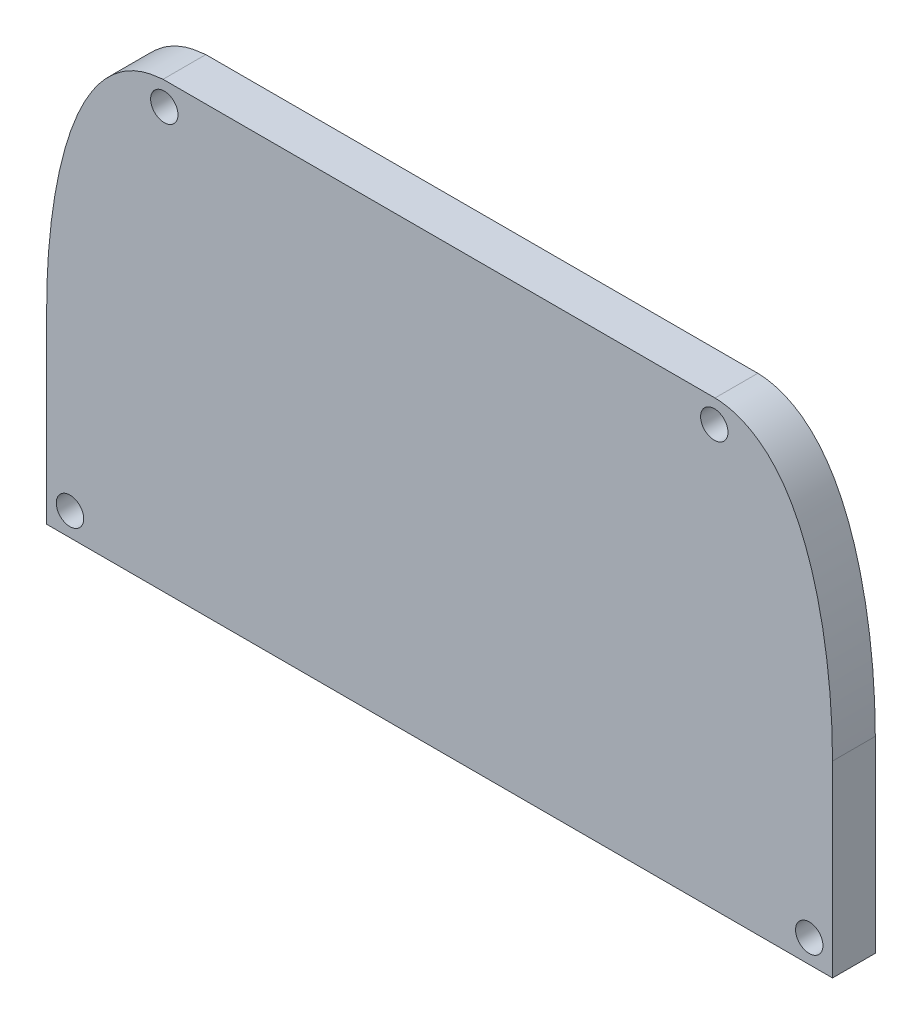
SolidWorks part; units mm, degrees
ref_plane "Front Plane" through (0, 0, 0) normal (0, 0, 1) x (1, 0, 0)
ref_plane "Top Plane" through (0, 0, 0) normal (0, 1, 0) x (1, 0, 0)
ref_plane "Right Plane" through (0, 0, 0) normal (1, 0, 0) x (0, 0, -1)
sketch "Sketch1" plane through (0, 0, 0) normal (0, 0, 1) x (1, 0, 0)
  line L0 (-29, 4.9329) -> (-29, 18.9593) construction
  line L1 (-29, 4.9329) -> (29, 4.9329) construction
  line L2 (29, 18.9593) -> (29, 4.9329) construction
  line L3 (-20.2196, 37.9329) -> (20.1267, 37.9329) construction
  line L4 (-29, 4.9329) -> (-29, 18.9593) construction
  line L5 (-29, 4.9329) -> (29, 4.9329) construction
  line L6 (29, 18.9593) -> (29, 4.9329) construction
  line L7 (-20.2196, 37.9329) -> (20.1267, 37.9329) construction
  line L8 (-20.2031, 37.6329) -> (20.1172, 37.6329)
  line L9 (28.7, 18.9573) -> (28.7, 5.2329)
  line L10 (-28.7, 5.2329) -> (28.7, 5.2329)
  line L11 (-28.7, 5.2329) -> (-28.7, 18.9574)
  spline S0 degree 2 poles (-31.9692, -1981.0344) (-29.7545, -9.9281) (-28.9753, 20.3809) (-28.956, 21.1325) (-28.9167, 21.8007) (-28.8758, 22.4979) (-28.8098, 23.2181) (-28.7437, 23.9403) (-28.6586, 24.6315) (-28.4799, 26.084) (-28.2121, 27.4233) (-27.9175, 28.8968) (-27.5367, 30.1575) (-27.0955, 31.6182) (-26.54, 32.811) (-26.2171, 33.5043) (-25.8726, 34.0804) (-25.4881, 34.7234) (-25.0615, 35.2597) (-24.6042, 35.8346) (-24.0818, 36.3005) (-23.8077, 36.5449) (-23.5308, 36.7481) (-23.2417, 36.9603) (-22.9324, 37.1389) (-22.6103, 37.3249) (-22.2891, 37.4608) (-21.9641, 37.5983) (-21.6205, 37.6954) (-21.3002, 37.7859) (-20.9286, 37.8453) (-20.7579, 37.8725) (-20.5753, 37.8935) (-17.3507, 38.2646) (1967.8393, 255.5742) knots -3.936313 -3.936313 -3.936313 0.0625 0.0625 0.125 0.125 0.1875 0.1875 0.25 0.25 0.375 0.375 0.5 0.5 0.625 0.625 0.6875 0.6875 0.75 0.75 0.8125 0.8125 0.84375 0.84375 0.875 0.875 0.90625 0.90625 0.9375 0.9375 0.96875 0.96875 0.984375 0.984375 2.300936 2.300936 2.300936 only from (-29, 18.9593) to (-20.2196, 37.9329) construction
  spline S1 degree 2 poles (-1977.1742, 141.4907) (9.4885, 38.8169) (20.4852, 37.9083) (20.6703, 37.893) (20.8404, 37.8684) (21.2069, 37.8154) (21.537, 37.7239) (21.7643, 37.6608) (21.9906, 37.5773) (22.4388, 37.4119) (22.8602, 37.1763) (23.1749, 37.0004) (23.4635, 36.7958) (23.748, 36.5941) (24.0261, 36.3514) (24.5413, 35.902) (25.0135, 35.3191) (25.3594, 34.8921) (25.6787, 34.3934) (25.9078, 34.0356) (26.1167, 33.6528) (26.3118, 33.295) (26.5032, 32.8894) (27.0665, 31.6959) (27.5124, 30.2375) (27.9021, 28.9627) (28.2027, 27.4702) (28.4749, 26.1185) (28.6558, 24.6546) (28.7415, 23.9614) (28.8083, 23.2347) (28.8748, 22.5113) (28.9161, 21.8119) (28.9558, 21.1393) (28.9752, 20.3865) (29.7594, -10.0157) (31.6782, -1981.0151) knots -1.71869 -1.71869 -1.71869 0.015625 0.015625 0.03125 0.03125 0.0625 0.0625 0.083333 0.083333 0.125 0.125 0.15625 0.15625 0.1875 0.1875 0.25 0.25 0.3 0.3 0.3375 0.3375 0.375 0.375 0.5 0.5 0.625 0.625 0.75 0.75 0.8125 0.8125 0.875 0.875 0.9375 0.9375 4.930379 4.930379 4.930379 only from (20.1267, 37.9329) to (29, 18.9593) construction
  spline S2 degree 2 poles (-29, 18.9593) (-28.9875, 19.9072) (-28.9753, 20.3809) (-28.956, 21.1325) (-28.9167, 21.8007) (-28.8758, 22.4979) (-28.8098, 23.2181) (-28.7437, 23.9403) (-28.6586, 24.6315) (-28.4799, 26.084) (-28.2121, 27.4233) (-27.9175, 28.8968) (-27.5367, 30.1575) (-27.0955, 31.6182) (-26.54, 32.811) (-26.2171, 33.5043) (-25.8726, 34.0804) (-25.4881, 34.7234) (-25.0615, 35.2597) (-24.6042, 35.8346) (-24.0818, 36.3005) (-23.8077, 36.5449) (-23.5308, 36.7481) (-23.2417, 36.9603) (-22.9324, 37.1389) (-22.6103, 37.3249) (-22.2891, 37.4608) (-21.9641, 37.5983) (-21.6205, 37.6954) (-21.3002, 37.7859) (-20.9286, 37.8453) (-20.7579, 37.8725) (-20.5753, 37.8935) (-20.537, 37.8979) (-20.2196, 37.9329) knots 0 0 0 0.0625 0.0625 0.125 0.125 0.1875 0.1875 0.25 0.25 0.375 0.375 0.5 0.5 0.625 0.625 0.6875 0.6875 0.75 0.75 0.8125 0.8125 0.84375 0.84375 0.875 0.875 0.90625 0.90625 0.9375 0.9375 0.96875 0.96875 0.984375 0.984375 1 1 1 construction
  spline S3 degree 2 poles (20.1267, 37.9329) (20.3861, 37.9165) (20.4852, 37.9083) (20.6703, 37.893) (20.8404, 37.8684) (21.2069, 37.8154) (21.537, 37.7239) (21.7643, 37.6608) (21.9906, 37.5773) (22.4388, 37.4119) (22.8602, 37.1763) (23.1749, 37.0004) (23.4635, 36.7958) (23.748, 36.5941) (24.0261, 36.3514) (24.5413, 35.902) (25.0135, 35.3191) (25.3594, 34.8921) (25.6787, 34.3934) (25.9078, 34.0356) (26.1167, 33.6528) (26.3118, 33.295) (26.5032, 32.8894) (27.0665, 31.6959) (27.5124, 30.2375) (27.9021, 28.9627) (28.2027, 27.4702) (28.4749, 26.1185) (28.6558, 24.6546) (28.7415, 23.9614) (28.8083, 23.2347) (28.8748, 22.5113) (28.9161, 21.8119) (28.9558, 21.1393) (28.9752, 20.3865) (28.9874, 19.9106) (29, 18.9593) knots 0 0 0 0.015625 0.015625 0.03125 0.03125 0.0625 0.0625 0.083333 0.083333 0.125 0.125 0.15625 0.15625 0.1875 0.1875 0.25 0.25 0.3 0.3 0.3375 0.3375 0.375 0.375 0.5 0.5 0.625 0.625 0.75 0.75 0.8125 0.8125 0.875 0.875 0.9375 0.9375 1 1 1 construction
  spline S4 degree 1 poles (-28.7, 18.9574) (-20.2031, 37.6329) knots 0 0 1 1 construction
  spline S5 degree 1 poles (20.1172, 37.6329) (28.7, 18.9573) knots 0 0 1 1 construction
  spline S6 degree 2 poles (-28.7, 18.9574) (-28.6922, 19.5495) (-28.6822, 20.0751) (-28.6783, 20.2529) (-28.6757, 20.3629) (-28.6703, 20.5617) (-28.6632, 20.7874) (-28.6482, 21.1914) (-28.6106, 21.9482) (-28.5163, 23.1936) (-28.3675, 24.5902) (-28.1922, 25.8371) (-28.0466, 26.695) (-27.9221, 27.3529) (-27.7681, 28.0843) (-27.607, 28.7711) (-27.4336, 29.4378) (-27.2573, 30.0537) (-27.0269, 30.7785) (-26.7898, 31.4448) (-26.536, 32.0848) (-26.2795, 32.6687) (-25.9472, 33.3431) (-25.627, 33.9166) (-25.2342, 34.5315) (-24.8389, 35.0682) (-24.3769, 35.6049) (-23.7716, 36.1955) (-22.8103, 36.9097) (-21.7788, 37.3494) (-21.2366, 37.4847) (-20.6299, 37.5979) (-20.2031, 37.6329) knots 0.000065 0.000065 0.000065 0.039109 0.050823 0.058631 0.06644 0.074249 0.085962 0.109389 0.156242 0.218712 0.281182 0.328035 0.35927 0.390506 0.421741 0.452976 0.484211 0.515446 0.546682 0.577917 0.609152 0.640387 0.671623 0.702858 0.734093 0.765328 0.796563 0.843416 0.905887 0.944931 0.960548 0.999592 0.999592 0.999592
  spline S7 degree 2 poles (20.1172, 37.6329) (21.1568, 37.6062) (22.7359, 36.9465) (23.72, 36.2416) (24.3173, 35.6683) (24.7922, 35.1263) (25.1938, 34.5895) (25.5802, 33.9943) (25.8807, 33.4639) (26.076, 33.0849) (26.2758, 32.6728) (26.5028, 32.1634) (26.76, 31.5234) (27, 30.8576) (27.2326, 30.1354) (27.4136, 29.5107) (27.5908, 28.8363) (27.7554, 28.1411) (27.9128, 27.3997) (28.0391, 26.7364) (28.187, 25.8709) (28.3648, 24.6129) (28.5147, 23.2105) (28.6098, 21.9608) (28.6478, 21.1995) (28.663, 20.7941) (28.6701, 20.5678) (28.6756, 20.3688) (28.6782, 20.258) (28.6822, 20.0795) (28.6921, 19.5518) (28.7, 18.9573) knots 0.000288 0.000288 0.000288 0.094005 0.156483 0.203341 0.23458 0.265819 0.297058 0.328297 0.351726 0.367346 0.390775 0.422014 0.453253 0.484492 0.515731 0.54697 0.578209 0.609448 0.640687 0.671926 0.718784 0.781262 0.84374 0.890599 0.914028 0.925742 0.933552 0.941362 0.949172 0.960886 0.999935 0.999935 0.999935
  dimension "D1" = 0.3
extrude "Boss-Extrude1" add sketch "Sketch1" along normal blind 3.125
sketch "Sketch2" plane through (0, 0, 3.125) normal (0, 0, 1) x (1, 0, 0)
  line L4 (-28.7, 18.9574) -> (-28.7, 5.2329)
  line L5 (-28.7, 5.2329) -> (28.7, 5.2329)
  line L6 (28.7, 5.2329) -> (28.7, 18.9573)
  line L7 (20.1172, 37.6329) -> (-20.2031, 37.6329)
  line L8 (-28.7, 18.9574) -> (-28.7, 5.2329)
  line L9 (-28.7, 5.2329) -> (28.7, 5.2329)
  line L10 (28.7, 5.2329) -> (28.7, 18.9573)
  line L11 (20.1172, 37.6329) -> (-20.2031, 37.6329)
  circle A0 centre (-27, 6.9329) radius 0.8 construction
  circle A1 centre (27, 6.9329) radius 0.8 construction
  circle A2 centre (20.0628, 35.9329) radius 0.8 construction
  circle A3 centre (-20.1097, 35.9329) radius 0.8 construction
  circle A4 centre (-27, 6.9329) radius 0.8 construction
  circle A5 centre (27, 6.9329) radius 0.8 construction
  circle A6 centre (20.0628, 35.9329) radius 0.8 construction
  circle A7 centre (-20.1097, 35.9329) radius 0.8 construction
  circle A8 centre (-27, 6.9329) radius 1
  circle A9 centre (-20.1097, 35.9329) radius 1
  circle A10 centre (20.0628, 35.9329) radius 1
  circle A11 centre (27, 6.9329) radius 1
  spline S2 degree 2 poles (-227.9214, -2952.9832) (90.3339, 58.3016) (-21.2366, 37.4847) (-21.7788, 37.3494) (-22.8103, 36.9097) (-23.7716, 36.1955) (-24.3769, 35.6049) (-24.8389, 35.0682) (-25.2342, 34.5315) (-25.627, 33.9166) (-25.9472, 33.3431) (-26.2795, 32.6687) (-26.536, 32.0848) (-26.7898, 31.4448) (-27.0269, 30.7785) (-27.2573, 30.0537) (-27.4336, 29.4378) (-27.607, 28.7711) (-27.7681, 28.0843) (-27.9221, 27.3529) (-28.0466, 26.695) (-28.1922, 25.8371) (-28.3675, 24.5902) (-28.5163, 23.1936) (-28.6106, 21.9482) (-28.6482, 21.1914) (-28.6632, 20.7874) (-28.6703, 20.5617) (-28.6757, 20.3629) (-28.6783, 20.2529) (-28.6822, 20.0751) (-29.6325, -30.2622) (-33.8955, -2980.9311) knots -9.998388 -9.998388 -9.998388 0.039109 0.054727 0.093771 0.156242 0.203094 0.23433 0.265565 0.2968 0.328035 0.35927 0.390506 0.421741 0.452976 0.484211 0.515446 0.546682 0.577917 0.609152 0.640387 0.671623 0.718475 0.780946 0.843416 0.890269 0.913695 0.925409 0.933217 0.941026 0.948835 0.960548 5.810746 5.810746 5.810746 only from (-20.2031, 37.6329) to (-28.7, 18.9574)
  spline S3 degree 2 poles (33.457, -2980.9554) (29.6365, -30.3918) (28.6822, 20.0795) (28.6782, 20.258) (28.6756, 20.3688) (28.6701, 20.5678) (28.663, 20.7941) (28.6478, 21.1995) (28.6098, 21.9608) (28.5147, 23.2105) (28.3648, 24.6129) (28.187, 25.8709) (28.0391, 26.7364) (27.9128, 27.3997) (27.7554, 28.1411) (27.5908, 28.8363) (27.4136, 29.5107) (27.2326, 30.1354) (27, 30.8576) (26.76, 31.5234) (26.5028, 32.1634) (26.2758, 32.6728) (26.076, 33.0849) (25.8807, 33.4639) (25.5802, 33.9943) (25.1938, 34.5895) (24.7922, 35.1263) (24.3173, 35.6683) (23.72, 36.2416) (22.7359, 36.9465) (-62.3322, 72.4806) (-878.3762, -2823.0797) knots -4.803992 -4.803992 -4.803992 0.039337 0.051051 0.058861 0.066671 0.074481 0.086195 0.109624 0.156483 0.218961 0.281439 0.328297 0.359536 0.390775 0.422014 0.453253 0.484492 0.515731 0.54697 0.578209 0.609448 0.632877 0.648497 0.671926 0.703165 0.734404 0.765643 0.796882 0.84374 0.906218 9.257963 9.257963 9.257963 only from (28.7, 18.9573) to (20.1172, 37.6329)
  spline S4 degree 2 poles (-20.2031, 37.6329) (-20.6299, 37.5979) (-21.2366, 37.4847) (-21.7788, 37.3494) (-22.8103, 36.9097) (-23.7716, 36.1955) (-24.3769, 35.6049) (-24.8389, 35.0682) (-25.2342, 34.5315) (-25.627, 33.9166) (-25.9472, 33.3431) (-26.2795, 32.6687) (-26.536, 32.0848) (-26.7898, 31.4448) (-27.0269, 30.7785) (-27.2573, 30.0537) (-27.4336, 29.4378) (-27.607, 28.7711) (-27.7681, 28.0843) (-27.9221, 27.3529) (-28.0466, 26.695) (-28.1922, 25.8371) (-28.3675, 24.5902) (-28.5163, 23.1936) (-28.6106, 21.9482) (-28.6482, 21.1914) (-28.6632, 20.7874) (-28.6703, 20.5617) (-28.6757, 20.3629) (-28.6783, 20.2529) (-28.6822, 20.0751) (-28.6922, 19.5495) (-28.7, 18.9574) knots 0.000065 0.000065 0.000065 0.039109 0.054727 0.093771 0.156242 0.203094 0.23433 0.265565 0.2968 0.328035 0.35927 0.390506 0.421741 0.452976 0.484211 0.515446 0.546682 0.577917 0.609152 0.640387 0.671623 0.718475 0.780946 0.843416 0.890269 0.913695 0.925409 0.933217 0.941026 0.948835 0.960548 0.999592 0.999592 0.999592
  spline S5 degree 2 poles (28.7, 18.9573) (28.6921, 19.5518) (28.6822, 20.0795) (28.6782, 20.258) (28.6756, 20.3688) (28.6701, 20.5678) (28.663, 20.7941) (28.6478, 21.1995) (28.6098, 21.9608) (28.5147, 23.2105) (28.3648, 24.6129) (28.187, 25.8709) (28.0391, 26.7364) (27.9128, 27.3997) (27.7554, 28.1411) (27.5908, 28.8363) (27.4136, 29.5107) (27.2326, 30.1354) (27, 30.8576) (26.76, 31.5234) (26.5028, 32.1634) (26.2758, 32.6728) (26.076, 33.0849) (25.8807, 33.4639) (25.5802, 33.9943) (25.1938, 34.5895) (24.7922, 35.1263) (24.3173, 35.6683) (23.72, 36.2416) (22.7359, 36.9465) (21.1568, 37.6062) (20.1172, 37.6329) knots 0.000288 0.000288 0.000288 0.039337 0.051051 0.058861 0.066671 0.074481 0.086195 0.109624 0.156483 0.218961 0.281439 0.328297 0.359536 0.390775 0.422014 0.453253 0.484492 0.515731 0.54697 0.578209 0.609448 0.632877 0.648497 0.671926 0.703165 0.734404 0.765643 0.796882 0.84374 0.906218 0.999935 0.999935 0.999935
  dimension "D1" = 0
  dimension "D2" = 0.2
extrude "Cut-Extrude1" cut sketch "Sketch2" against normal through all contours A8 | A9 | A10 | A11 region at (-27, 6.9329, 3.125) region at (-20.1097, 35.9329, 3.125) region at (20.0628, 35.9329, 3.125) region at (27, 6.9329, 3.125)
